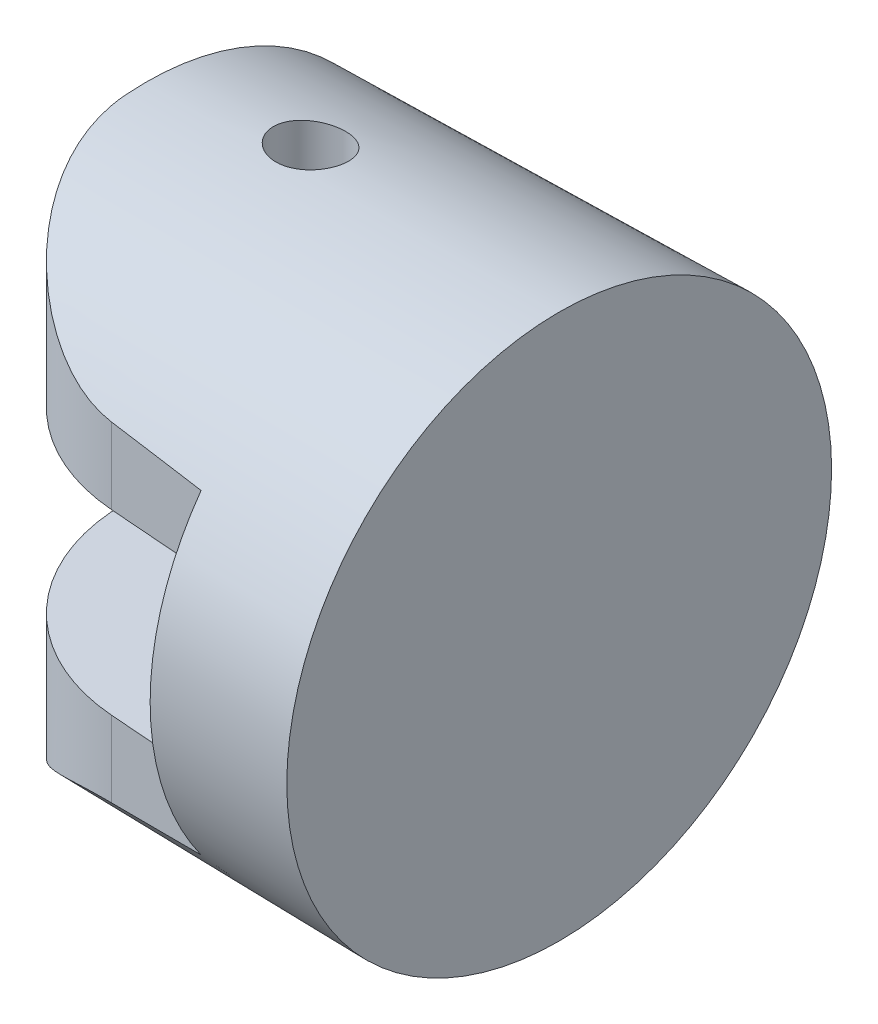
SolidWorks part; units mm, degrees
material "1060 Alloy"
ref_plane "Front Plane" through (0, 0, 0) normal (0, 0, 1) x (1, 0, 0)
ref_plane "Top Plane" through (0, 0, 0) normal (0, 1, 0) x (1, 0, 0)
ref_plane "Right Plane" through (0, 0, 0) normal (1, 0, 0) x (0, 0, -1)
sketch "Sketch1" plane through (0, 0, 0) normal (1, 0, 0) x (0, 0, -1)
  circle A0 centre (0, 0) radius 10
  dimension "D1" = 20
extrude "Boss-Extrude1" add sketch "Sketch1" along normal blind 18
sketch "Sketch2" plane through (0, 0, 0) normal (0, 1, 0) x (1, 0, 0)
  line L0 (10, 12.12) -> (10, 9.06)
  line L1 (-2.6, 12.12) -> (10, 12.12)
  line L2 (-2.6, 12.12) -> (-2.6, -11.6)
  line L3 (-2.6, -11.6) -> (10, -11.6)
  line L5 (10, 9.06) -> (0, 9.06)
  line L6 (0, 10) -> (0, -10) construction
  line L7 (0, 9.06) -> (0, -0.75)
  line L8 (10, -11.6) -> (10, -8)
  line L9 (10, -8) -> (6.466, -7.7296)
  line L10 (18, -10) -> (18, 10) construction
  arc A0 (0, -0.75) -> (6.466, -7.7296) centre (7, -0.75) ccw
  dimension "D5" = 7
  dimension "D1" = 23.72
  dimension "D2" = 12.6
  dimension "D3" = 8
  dimension "D4" = 9.06
  dimension "D6" = 8
  dimension "D7" = 3.6
  dimension "D8" = 2
  dimension "D9" = 10.85
extrude "Cut-Extrude1" cut sketch "Sketch2" against normal blind 18 and the other way blind 18
sketch "Sketch3" plane through (0, 0, 0) normal (0, 1, 0) x (1, 0, 0)
  line L0 (5, 1) -> (18, 1) construction
  line L1 (18, -10) -> (18, 10) construction
  circle A0 centre (5, 1) radius 1.25
  dimension "D1" = 2.5
  dimension "D2" = 9
  dimension "D3" = 13
extrude "Cut-Extrude2" cut sketch "Sketch3" against normal through all and the other way through all
sketch "Sketch5" plane through (18, 0, 0) normal (1, 0, 0) x (0, 0, -1)
  circle A0 centre (0, 0) radius 10
  dimension "D1" = 20
extrude "Cut-Extrude-Thin2" cut sketch "Sketch5" against normal blind 23.25 draft 1 thin draft outward yes thin type one direction wall 10
fillet "Fillet1" radius 0.5 1 edges at (0, 0, -9.06)
chamfer "Chamfer1" distance 1 angle 45 1 edges at (10, 0, -9.8604) first distance on face at (10, 0, -9.4602)
sketch "Sketch7" plane through (0, 0, 0) normal (0, 1, 0) x (1, 0, 0)
  line L1 (-0.3343, 9.06) -> (10, 9.06)
  line L2 (-0.3343, 9.06) -> (-0.3343, -8)
  line L3 (-0.3343, -8) -> (10, -8)
  line L4 (10, 9.06) -> (10, -8)
extrude "Cut-Extrude4" cut sketch "Sketch7" against normal mid plane 6.5
sketch "Sketch8" plane through (0, 0, 0) normal (0, 1, 0) x (1, 0, 0)
  line L1 (15.08, 11.5998) -> (20.5717, 11.5998)
  line L2 (15.08, 11.5998) -> (15.08, -11.3196)
  line L3 (15.08, -11.3196) -> (20.5717, -11.3196)
  line L4 (20.5717, 11.5998) -> (20.5717, -11.3196)
  dimension "D1" = 15.08
extrude "Cut-Extrude5" cut sketch "Sketch8" against normal mid plane 24.7
